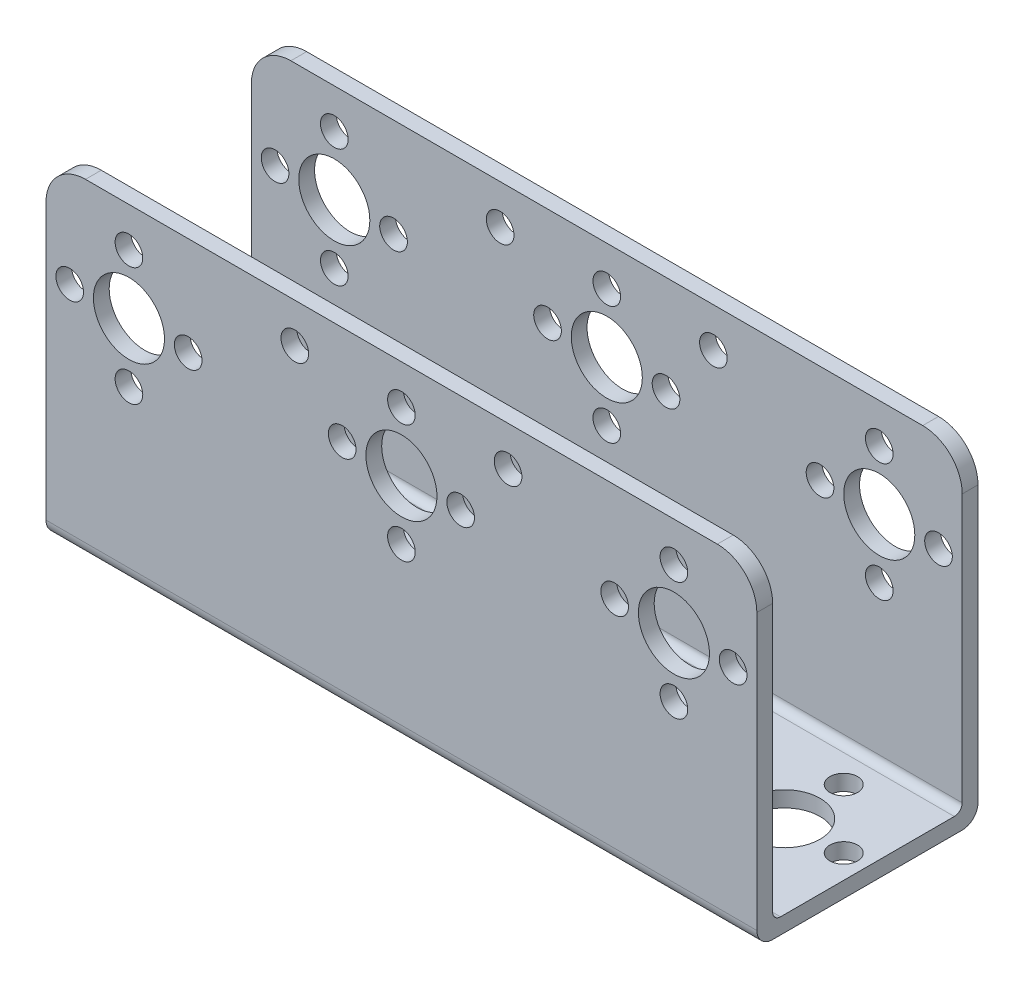
SolidWorks part; units mm, degrees
ref_plane "Piano frontale" through (0, 0, 0) normal (0, 0, 1) x (1, 0, 0)
ref_plane "Piano superiore" through (0, 0, 0) normal (0, 1, 0) x (1, 0, 0)
ref_plane "Piano destro" through (0, 0, 0) normal (1, 0, 0) x (0, 0, -1)
sketch "Schizzo1" plane through (0, 0, 0) normal (0, 0, 1) x (1, 0, 0)
  line L1 (0, 0) -> (90, 0)
  line L2 (0, 0) -> (0, 36.8605)
  line L3 (5, 41.8605) -> (85, 41.8605)
  line L4 (90, 0) -> (90, 36.8605)
  arc A0 (85, 41.8605) -> (90, 36.8605) centre (85, 36.8605) cw
  arc A1 (0, 36.8605) -> (5, 41.8605) centre (5, 36.8605) cw
  point P7 (90, 41.8605)
  point P10 (0, 41.8605)
  dimension "D3" = 5
  dimension "D1" = 90
  dimension "D2" = 41.8605
extrude "Estrusione-Estrusione1" add sketch "Schizzo1" against normal blind 2
sketch "Schizzo2" plane through (0, 0, 0) normal (0, 1, 0) x (1, 0, 0)
  line L1 (0, 0) -> (90, 0)
  line L2 (0, 0) -> (0, 28)
  line L3 (0, 28) -> (90, 28)
  line L4 (90, 0) -> (90, 28)
  dimension "D1" = 90
  dimension "D2" = 28
extrude "Estrusione-Estrusione2" add sketch "Schizzo2" along normal blind 2
ref_plane "Piano1" through (0, 0, -28) normal (0, 0, 1) x (1, 0, 0)
sketch "Schizzo4" plane through (0, 0, -28) normal (0, 0, 1) x (1, 0, 0)
  line L4 (90, 0) -> (90, 36.8605)
  line L5 (85, 41.8605) -> (5, 41.8605)
  line L6 (0, 36.8605) -> (0, 0)
  line L7 (0, 0) -> (90, 0)
  line L8 (90, 0) -> (90, 36.8605)
  line L9 (85, 41.8605) -> (5, 41.8605)
  line L10 (0, 36.8605) -> (0, 0)
  line L11 (0, 0) -> (90, 0)
  arc A2 (90, 36.8605) -> (85, 41.8605) centre (85, 36.8605) ccw
  arc A3 (5, 41.8605) -> (0, 36.8605) centre (5, 36.8605) ccw
  arc A4 (90, 36.8605) -> (85, 41.8605) centre (85, 36.8605) ccw
  arc A5 (5, 41.8605) -> (0, 36.8605) centre (5, 36.8605) ccw
  dimension "D1" = 0
extrude "Estrusione-Estrusione3" add sketch "Schizzo4" along normal blind 2
sketch "Schizzo5" plane through (0, 0, 0) normal (0, 0, 1) x (1, 0, 0)
  line L0 (10.5, 21.8605) -> (45, 21.8605) construction
  line L1 (85, 41.8605) -> (5, 41.8605) construction
  line L2 (0, 36.8605) -> (0, 0) construction
  line L3 (10.5, 29.3605) -> (45, 29.3605) construction
  line L4 (90, 0) -> (90, 36.8605) construction
  line L5 (45, 29.3605) -> (79.5, 29.3605) construction
  line L6 (45, 21.8605) -> (79.5, 21.8605) construction
  line L7 (10.5, 36.8605) -> (45, 36.8605) construction
  line L8 (45, 36.8605) -> (79.5, 36.8605) construction
  circle A0 centre (10.5, 29.3605) radius 4.5
  circle A1 centre (45, 29.3605) radius 4.5
  circle A2 centre (79.5, 29.3605) radius 4.5
  circle A3 centre (10.5, 36.8605) radius 1.75
  circle A4 centre (3, 29.3605) radius 1.75
  circle A5 centre (10.5, 21.8605) radius 1.75
  circle A6 centre (18, 29.3605) radius 1.75
  circle A7 centre (37.5, 29.3605) radius 1.75
  circle A8 centre (45, 36.8605) radius 1.75
  circle A9 centre (79.5, 36.8605) radius 1.75
  circle A10 centre (72, 29.3605) radius 1.75
  circle A11 centre (45, 21.8605) radius 1.75
  circle A12 centre (79.5, 21.8605) radius 1.75
  circle A13 centre (87, 29.3605) radius 1.75
  circle A14 centre (31.5, 36.8605) radius 1.75
  circle A15 centre (58.5, 36.8605) radius 1.75
  circle A16 centre (52.5, 29.3605) radius 1.75
  dimension "D1" = 9
  dimension "D2" = 6
  dimension "D3" = 6
  dimension "D4" = 8
  dimension "D5" = 3.5
  dimension "D6" = 7.5
  dimension "D7" = 7.5
  dimension "D8" = 7.5
  dimension "D9" = 7.5
  dimension "D10" = 7.5
  dimension "D11" = 7.5
  dimension "D12" = 7.5
  dimension "D13" = 7.5
  dimension "D14" = 7.5
  dimension "D15" = 7.5
  dimension "D16" = 7.5
  dimension "D17" = 7.5
  dimension "D18" = 13.5
  dimension "D19" = 13.5
extrude "Taglio-Estrusione1" cut sketch "Schizzo5" against normal through all
fillet "Raccordo1" radius 2 1 edges at (45, 0, -28)
fillet "Raccordo2" radius 2 1 edges at (45, 0, 0)
fillet "Raccordo3" radius 1 1 edges at (45, 2, -2)
fillet "Raccordo4" radius 1 1 edges at (45, 2, -26)
sketch "Schizzo6" plane through (0, 0, 0) normal (0, 1, 0) x (1, 0, 0)
  line L0 (0, 14) -> (90, 14) construction
  line L1 (0, 25) -> (0, 3) construction
  line L2 (90, 3) -> (90, 25) construction
  line L3 (10.5, 3) -> (10.5, 14) construction
  line L4 (0, 3) -> (90, 3) construction
  line L5 (10.5, 14) -> (10.5, 25) construction
  line L6 (90, 25) -> (0, 25) construction
  line L7 (45, 3) -> (45, 14) construction
  line L8 (45, 14) -> (45, 25) construction
  line L9 (79.5, 3) -> (79.5, 14) construction
  line L10 (79.5, 14) -> (79.5, 25) construction
  circle A0 centre (45, 14) radius 4.5
  circle A1 centre (10.5, 14) radius 4.5
  circle A2 centre (79.5, 14) radius 4.5
  circle A3 centre (10.5, 21.5) radius 1.75
  circle A4 centre (3, 14) radius 1.75
  circle A5 centre (10.5, 6.5) radius 1.75
  circle A6 centre (18, 14) radius 1.75
  circle A7 centre (37.5, 14) radius 1.75
  circle A8 centre (45, 21.5) radius 1.75
  circle A9 centre (79.5, 21.5) radius 1.75
  circle A10 centre (79.5, 6.5) radius 1.75
  circle A11 centre (45, 6.5) radius 1.75
  circle A12 centre (52.5, 14) radius 1.75
  circle A13 centre (87, 14) radius 1.75
  circle A14 centre (72, 14) radius 1.75
  dimension "D1" = 9
  dimension "D4" = 3.5
  dimension "D2" = 10.5
  dimension "D3" = 10.5
  dimension "D5" = 7.5
  dimension "D6" = 7.5
  dimension "D7" = 7.5
  dimension "D8" = 7.5
  dimension "D9" = 7.5
  dimension "D10" = 7.5
  dimension "D11" = 7.5
  dimension "D12" = 7.5
  dimension "D13" = 7.5
  dimension "D14" = 7.5
  dimension "D15" = 7.5
  dimension "D16" = 7.5
extrude "Taglio-Estrusione2" cut sketch "Schizzo6" along normal through all
